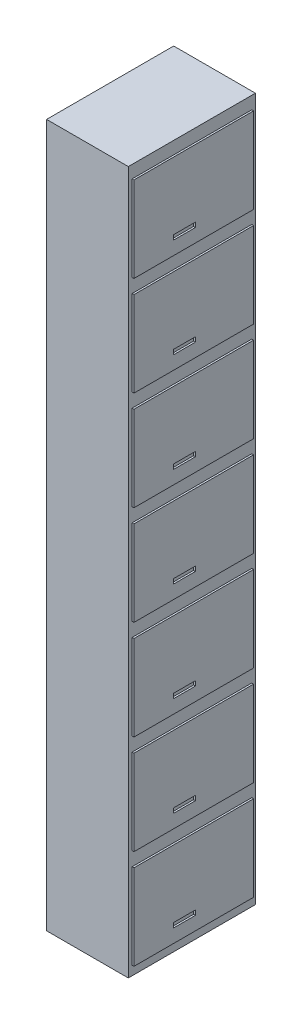
SolidWorks part; units mm, degrees
ref_plane "Front Plane" through (0, 0, 0) normal (0, 0, 1) x (1, 0, 0)
ref_plane "Top Plane" through (0, 0, 0) normal (0, 1, 0) x (1, 0, 0)
ref_plane "Right Plane" through (0, 0, 0) normal (1, 0, 0) x (0, 0, -1)
sketch "Sketch1" plane through (0, 0, 0) normal (0, 0, 1) x (1, 0, 0)
  line L0 (313.062, 4179.9863) -> (-136.938, 4179.9863)
  line L1 (-136.938, 4179.9863) -> (-136.938, 309.9863)
  line L2 (-136.938, 309.9863) -> (313.062, 309.9863)
  line L5 (313.062, 309.9863) -> (313.062, 4179.9863)
  dimension "D1" = 450
  dimension "D2" = 3870
extrude "Boss-Extrude1" add sketch "Sketch1" along normal blind 700
sketch "Sketch3" plane through (313.062, 0, 0) normal (1, 0, 0) x (0, 0, -1)
  line L1 (-678.863, 359.9863) -> (-20, 359.9863)
  line L2 (-678.863, 359.9863) -> (-678.863, 829.9863)
  line L3 (-678.863, 829.9863) -> (-20, 829.9863)
  line L4 (-20, 359.9863) -> (-20, 829.9863)
  line L5 (-700, 309.9863) -> (0, 309.9863) construction
  line L6 (-678.863, 906.7588) -> (-20, 906.7588)
  line L7 (-461.6648, -2274.1108) -> (-340.5919, -2274.1108)
  line L8 (-461.6648, -2274.1108) -> (-461.6648, -2299.9132)
  line L9 (-461.6648, -2299.9132) -> (-340.5919, -2299.9132)
  line L10 (-340.5919, -2274.1108) -> (-340.5919, -2299.9132)
  line L11 (-678.863, 906.7588) -> (-678.863, 1376.7588)
  line L12 (-678.863, 1376.7588) -> (-20, 1376.7588)
  line L13 (-20, 906.7588) -> (-20, 1376.7588)
  line L14 (-461.6648, -1727.3383) -> (-340.5919, -1727.3383)
  line L15 (-461.6648, -1753.1407) -> (-340.5919, -1753.1407)
  line L16 (-461.6648, -1727.3383) -> (-461.6648, -1753.1407)
  line L17 (-340.5919, -1727.3383) -> (-340.5919, -1753.1407)
  line L18 (-678.863, 1453.5313) -> (-20, 1453.5313)
  line L19 (-678.863, 1453.5313) -> (-678.863, 1923.5313)
  line L20 (-678.863, 1923.5313) -> (-20, 1923.5313)
  line L21 (-20, 1453.5313) -> (-20, 1923.5313)
  line L26 (-678.863, 2000.3038) -> (-20, 2000.3038)
  line L27 (-678.863, 2000.3038) -> (-678.863, 2470.3038)
  line L28 (-678.863, 2470.3038) -> (-20, 2470.3038)
  line L29 (-20, 2000.3038) -> (-20, 2470.3038)
  line L36 (-678.863, 2547.0763) -> (-20, 2547.0763)
  line L37 (-678.863, 2547.0763) -> (-678.863, 3017.0763)
  line L38 (-678.863, 3017.0763) -> (-20, 3017.0763)
  line L39 (-20, 2547.0763) -> (-20, 3017.0763)
  line L44 (-678.863, 3093.8488) -> (-20, 3093.8488)
  line L45 (-678.863, 3093.8488) -> (-678.863, 3563.8488)
  line L46 (-678.863, 3563.8488) -> (-20, 3563.8488)
  line L47 (-20, 3093.8488) -> (-20, 3563.8488)
  line L48 (-461.6648, 459.7517) -> (-340.5919, 459.7517)
  line L49 (-461.6648, 433.9492) -> (-340.5919, 433.9492)
  line L50 (-461.6648, 459.7517) -> (-461.6648, 433.9492)
  line L51 (-340.5919, 459.7517) -> (-340.5919, 433.9492)
  line L52 (-678.863, 3640.6212) -> (-20, 3640.6212)
  line L53 (-678.863, 3640.6212) -> (-678.863, 4110.6212)
  line L54 (-678.863, 4110.6212) -> (-20, 4110.6212)
  line L55 (-20, 3640.6212) -> (-20, 4110.6212)
  line L56 (-461.6648, 1006.5241) -> (-340.5919, 1006.5241)
  line L57 (-461.6648, 980.7217) -> (-340.5919, 980.7217)
  line L58 (-461.6648, 1006.5241) -> (-461.6648, 980.7217)
  line L59 (-340.5919, 1006.5241) -> (-340.5919, 980.7217)
  line L64 (-461.6648, 1553.2966) -> (-340.5919, 1553.2966)
  line L65 (-461.6648, 1527.4942) -> (-340.5919, 1527.4942)
  line L66 (-461.6648, 1553.2966) -> (-461.6648, 1527.4942)
  line L67 (-340.5919, 1553.2966) -> (-340.5919, 1527.4942)
  line L72 (-461.6648, 2100.0691) -> (-340.5919, 2100.0691)
  line L73 (-461.6648, 2074.2667) -> (-340.5919, 2074.2667)
  line L74 (-461.6648, 2100.0691) -> (-461.6648, 2074.2667)
  line L75 (-340.5919, 2100.0691) -> (-340.5919, 2074.2667)
  line L80 (-461.6648, 2646.8416) -> (-340.5919, 2646.8416)
  line L81 (-461.6648, 2621.0392) -> (-340.5919, 2621.0392)
  line L82 (-461.6648, 2646.8416) -> (-461.6648, 2621.0392)
  line L83 (-340.5919, 2646.8416) -> (-340.5919, 2621.0392)
  line L88 (-461.6648, 3193.6141) -> (-340.5919, 3193.6141)
  line L89 (-461.6648, 3167.8117) -> (-340.5919, 3167.8117)
  line L90 (-461.6648, 3193.6141) -> (-461.6648, 3167.8117)
  line L91 (-340.5919, 3193.6141) -> (-340.5919, 3167.8117)
  line L96 (-461.6648, 3740.3866) -> (-340.5919, 3740.3866)
  line L97 (-461.6648, 3714.5842) -> (-340.5919, 3714.5842)
  line L98 (-461.6648, 3740.3866) -> (-461.6648, 3714.5842)
  line L99 (-340.5919, 3740.3866) -> (-340.5919, 3714.5842)
  line L116 (-678.863, 4734.1662) -> (-678.863, 5204.1662) [skipped]
  line L117 (-678.863, 5204.1662) -> (-20, 5204.1662) [skipped]
  line L118 (-20, 4734.1662) -> (-20, 5204.1662) [skipped]
  line L119 (-678.863, 5280.9387) -> (-20, 5280.9387) [skipped]
  line L120 (-678.863, 5280.9387) -> (-678.863, 5750.9387) [skipped]
  line L121 (-678.863, 5750.9387) -> (-20, 5750.9387) [skipped]
  line L122 (-20, 5280.9387) -> (-20, 5750.9387) [skipped]
  line L123 (-678.863, 5827.7112) -> (-20, 5827.7112) [skipped]
  line L124 (-678.863, 5827.7112) -> (-678.863, 6297.7112) [skipped]
  line L125 (-678.863, 6297.7112) -> (-20, 6297.7112) [skipped]
  line L126 (-20, 5827.7112) -> (-20, 6297.7112) [skipped]
  line L127 (-678.863, 6374.4837) -> (-20, 6374.4837) [skipped]
  line L128 (-678.863, 6374.4837) -> (-678.863, 6844.4837) [skipped]
  line L129 (-678.863, 6844.4837) -> (-20, 6844.4837) [skipped]
  line L130 (-20, 6374.4837) -> (-20, 6844.4837) [skipped]
  line L131 (-678.863, 6921.2562) -> (-20, 6921.2562) [skipped]
  line L132 (-678.863, 6921.2562) -> (-678.863, 7391.2562) [skipped]
  line L133 (-678.863, 7391.2562) -> (-20, 7391.2562) [skipped]
  line L134 (-20, 6921.2562) -> (-20, 7391.2562) [skipped]
  line L135 (-678.863, 7468.0286) -> (-20, 7468.0286) [skipped]
  line L136 (-678.863, 7468.0286) -> (-678.863, 7938.0286) [skipped]
  line L137 (-678.863, 7938.0286) -> (-20, 7938.0286) [skipped]
  line L138 (-20, 7468.0286) -> (-20, 7938.0286) [skipped]
  line L139 (-678.863, 4187.3937) -> (-678.863, 4657.3937) [skipped]
  line L140 (-678.863, 4657.3937) -> (-20, 4657.3937) [skipped]
  line L141 (-20, 4187.3937) -> (-20, 4657.3937) [skipped]
  line L142 (-678.863, 4734.1662) -> (-20, 4734.1662) [skipped]
  line L143 (-461.6648, 4833.9315) -> (-340.5919, 4833.9315) [skipped]
  line L144 (-461.6648, 4808.1291) -> (-340.5919, 4808.1291) [skipped]
  line L145 (-461.6648, 4833.9315) -> (-461.6648, 4808.1291) [skipped]
  line L146 (-340.5919, 4833.9315) -> (-340.5919, 4808.1291) [skipped]
  line L147 (-678.863, 4187.3937) -> (-20, 4187.3937) [skipped]
  line L148 (-461.6648, 4287.1591) -> (-340.5919, 4287.1591) [skipped]
  line L149 (-461.6648, 4261.3567) -> (-340.5919, 4261.3567) [skipped]
  line L150 (-461.6648, 4287.1591) -> (-461.6648, 4261.3567) [skipped]
  line L151 (-340.5919, 4287.1591) -> (-340.5919, 4261.3567) [skipped]
  line L152 (-461.6648, -1180.5658) -> (-340.5919, -1180.5658) [skipped]
  line L153 (-461.6648, -1206.3682) -> (-340.5919, -1206.3682) [skipped]
  line L154 (-461.6648, -1180.5658) -> (-461.6648, -1206.3682) [skipped]
  line L155 (-340.5919, -1180.5658) -> (-340.5919, -1206.3682) [skipped]
  line L156 (-461.6648, -633.7933) -> (-340.5919, -633.7933) [skipped]
  line L157 (-461.6648, -659.5957) -> (-340.5919, -659.5957) [skipped]
  line L158 (-461.6648, -633.7933) -> (-461.6648, -659.5957) [skipped]
  line L159 (-340.5919, -633.7933) -> (-340.5919, -659.5957) [skipped]
  line L160 (-461.6648, -87.0208) -> (-340.5919, -87.0208) [skipped]
  line L161 (-461.6648, -112.8232) -> (-340.5919, -112.8232) [skipped]
  line L162 (-461.6648, -87.0208) -> (-461.6648, -112.8232) [skipped]
  line L163 (-340.5919, -87.0208) -> (-340.5919, -112.8232) [skipped]
  dimension "D1" = 470
  dimension "D3" = 50
  dimension "D4" = 14
extrude "Boss-Extrude3" add sketch "Sketch3" along normal blind 10 contours L1 L4 L3 L2 L7 L10 L9 L8 | L18 L21 L20 L19 | L6 L13 L12 L11 L14 L17 L15 L16 | L26 L29 L28 L27 | L36 L39 L38 L37 | L44 L47 L46 L45 L48 L51 L49 L50 | L52 L55 L54 L53 L56 L59 L57 L58 | L64 L67 L65 L66 | L72 L75 L73 L74 | L80 L83 L81 L82 | L88 L91 L89 L90 | L96 L99 L97 L98 region at (313.062, 596.496, 348.9046) region at (313.062, 1143.2685, 348.9046) region at (313.062, 1690.041, 348.9046) region at (313.062, 2236.8134, 348.9046) region at (313.062, 2783.5859, 348.9046) region at (313.062, 3330.3584, 348.9046) region at (313.062, 3877.1309, 348.9046)
